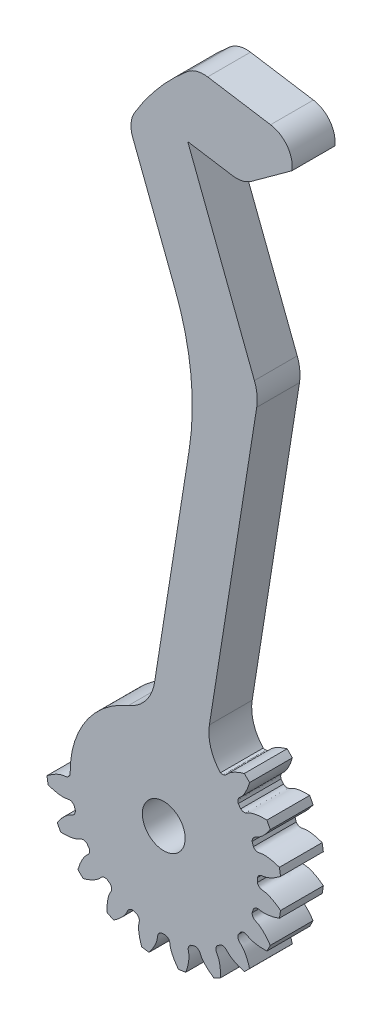
SolidWorks part; units mm, degrees
note: '?' marks a value the reader was unsure of.
material "聚脂树脂"
ref_plane "前视基准面" through (0, 0, 0) normal (0, 0, 1) x (1, 0, 0)
ref_plane "上视基准面" through (0, 0, 0) normal (0, 1, 0) x (1, 0, 0)
ref_plane "右视基准面" through (0, 0, 0) normal (1, 0, 0) x (0, 0, -1)
other "Configuration Table"
sketch "草图1" plane through (0, 0, 0) normal (0, 0, 1) x (1, 0, 0)
  circle A0 centre (0, 0) radius 13.75
extrude "凸台-拉伸1" add sketch "草图1" along normal blind 5
ref_axis "基准轴1" through (0, 0, -1.5) along (0, 0, 1)?
sketch "草图2" plane through (0, 0, 0) normal (0, 0, 1) x (1, 0, 0)
  line L0 (0, 0) -> (0, 13.75) construction
  circle A0 centre (0, 0) radius 13.75 construction
  arc A1 (0.2416, 10.9348) -> (-0.2416, 10.9348) centre (0, 0) ccw
  arc A2 (3.9764, 15.6228) -> (-3.9764, 15.6228) centre (0, 0) ccw
  spline S0 degree 3 poles (0.2416, 10.9348) (0.764, 11.1168) (0.6964, 11.4839) (0.7661, 11.8375) (0.7736, 11.8719) (0.7829, 11.9108) (0.7941, 11.954) (0.8075, 12.0015) (0.8231, 12.0532) (0.8413, 12.1091) (0.8621, 12.169) (0.8857, 12.2329) (0.9123, 12.3007) (0.9421, 12.3723) (0.9752, 12.4476) (1.0117, 12.5264) (1.0519, 12.6088) (1.0959, 12.6945) (1.1438, 12.7834) (1.1957, 12.8755) (1.2519, 12.9705) (1.3125, 13.0684) (1.3775, 13.1691) (1.4472, 13.2723) (1.5216, 13.3779) (1.601, 13.4858) (1.6853, 13.5958) (1.7747, 13.7078) (1.8694, 13.8216) (1.9693, 13.937) (2.0748, 14.0539) (2.1857, 14.1721) (2.3023, 14.2914) (2.4246, 14.4116) (2.5527, 14.5326) (2.6866, 14.6542) (2.8265, 14.7761) (2.9725, 14.8983) (3.1245, 15.0204) (3.2826, 15.1424) (3.4469, 15.2639) (3.6768, 15.427) (3.8549, 15.5454) (3.9764, 15.6228) knots 0 0 0 0 0.165916 0.170906 0.176664 0.183189 0.190482 0.198542 0.207371 0.216967 0.22733 0.238462 0.250361 0.263027 0.276462 0.290664 0.305634 0.321371 0.337876 0.355149 0.37319 0.391998 0.411574 0.431917 0.453028 0.474907 0.497554 0.520968 0.54515 0.570099 0.595817 0.622302 0.649554 0.677575 0.706363 0.735918 0.766242 0.797333 0.829191 0.861818 0.895212 0.929373 1 1 1 1
  spline S1 degree 3 poles (-0.2416, 10.9348) (-0.764, 11.1168) (-0.6964, 11.4839) (-0.7661, 11.8375) (-0.7736, 11.8719) (-0.7829, 11.9108) (-0.7941, 11.954) (-0.8075, 12.0015) (-0.8231, 12.0532) (-0.8413, 12.1091) (-0.8621, 12.169) (-0.8857, 12.2329) (-0.9123, 12.3007) (-0.9421, 12.3723) (-0.9752, 12.4476) (-1.0117, 12.5264) (-1.0519, 12.6088) (-1.0959, 12.6945) (-1.1438, 12.7834) (-1.1957, 12.8755) (-1.2519, 12.9705) (-1.3125, 13.0684) (-1.3775, 13.1691) (-1.4472, 13.2723) (-1.5216, 13.3779) (-1.601, 13.4858) (-1.6853, 13.5958) (-1.7747, 13.7078) (-1.8694, 13.8216) (-1.9693, 13.937) (-2.0748, 14.0539) (-2.1857, 14.1721) (-2.3023, 14.2914) (-2.4246, 14.4116) (-2.5527, 14.5326) (-2.6866, 14.6542) (-2.8265, 14.7761) (-2.9725, 14.8983) (-3.1245, 15.0204) (-3.2826, 15.1424) (-3.4469, 15.2639) (-3.6768, 15.427) (-3.8549, 15.5454) (-3.9764, 15.6228) knots 0 0 0 0 0.165916 0.170906 0.176664 0.183189 0.190482 0.198542 0.207371 0.216967 0.22733 0.238462 0.250361 0.263027 0.276462 0.290664 0.305634 0.321371 0.337876 0.355149 0.37319 0.391998 0.411574 0.431917 0.453028 0.474907 0.497554 0.520968 0.54515 0.570099 0.595817 0.622302 0.649554 0.677575 0.706363 0.735918 0.766242 0.797333 0.829191 0.861818 0.895212 0.929373 1 1 1 1
extrude "切除-拉伸1" cut sketch "草图2" along normal through all
pattern_circular "阵列(圆周)1" count 20 every 18 about axis through (0, 0, -1.5) along (0, 0, 1) of "切除-拉伸1"
sketch "草图6" plane through (0, 0, 0) normal (0, 0, -1) x (-1, 0, 0)
  line L0 (0, 0) -> (-10.311, 65.1009) construction
  line L1 (0, 0) -> (38.9643, 6.1713) construction
  line L2 (0, 0) -> (-30.4582, -4.8241) construction
  line L3 (-12.3461, -1.9554) -> (-25.9319, 83.8219) construction
  line L4 (3.21, 0.5084) -> (-2.4333, 36.1385)
  line L5 (-3.21, -0.5084) -> (-8.8532, 35.1216)
  line L6 (-8.8532, 35.1216) -> (-14.8239, 72.819)
  line L7 (-14.8239, 72.819) -> (-21.4537, 55.5478) construction
  line L8 (-14.8239, 72.819) -> (-7.9754, 90.6601) construction
  line L9 (-14.8239, 72.819) -> (-11.7149, 80.9182)
  line L10 (-3.21, -0.5084) -> (3.21, 0.5084)
  line L11 (-25.2081, 79.2523) -> (-40.1052, 40.4441)
  line L12 (-40.1052, 40.4441) -> (0.9522, 46.947)
  line L13 (0.9522, 46.947) -> (-25.2081, 79.2523)
  line L14 (-15.4429, 76.7274) -> (6.8442, 49.2051)
  line L15 (-17.6993, 31.8433) -> (-2.8022, 70.6515)
  line L16 (-2.8022, 70.6515) -> (-43.8596, 64.1486)
  line L17 (-43.8596, 64.1486) -> (-17.6993, 31.8433)
  line L18 (-2.4333, 36.1385) -> (-3.0647, 40.1255)
  line L19 (-3.0647, 40.1255) -> (-4.2206, 47.4234)
  line L20 (-4.2206, 47.4234) -> (4.1358, 69.1925)
  line L21 (-14.8239, 72.819) -> (-15.4429, 76.7274)
  line L22 (-15.4429, 76.7274) -> (-3.8174, 78.5687)
  circle A0 centre (0, 0) radius 12.5 construction
  circle A1 centre (-21.4537, 55.5478) radius 24 construction
  circle A2 centre (-21.4537, 55.5478) radius 27.1754 construction
  arc A3 (-11.7149, 80.9182) -> (-2.4333, 36.1385) centre (-21.4537, 55.5478) cw
  arc A4 (-12.8529, 77.9537) -> (-8.8532, 35.1216) centre (-21.4537, 55.5478) cw
  arc A5 (6.8442, 49.2051) -> (-2.0884, 33.9611) centre (-21.4537, 55.5478) cw
  arc A6 (0.3229, 47.7241) -> (-0.0355, 46.7905) centre (0.9522, 46.947) cw
  arc A7 (-11.061, 82.6216) -> (4.1358, 69.1925) centre (-21.4537, 55.5478) cw
  dimension "D1" = 25
  dimension "D4" = 48
  dimension "D5" = 30
  dimension "D8" = 29
  dimension "D9" = 1
  dimension "D10" = 29
  dimension "D2" = 6.5
  dimension "D3" = 58.22
  dimension "D6" = 60
  dimension "D7" = 6
  dimension "D11" = 7
extrude "凸台-拉伸2" add sketch "草图6" against normal blind 5
ref_plane "基准面1" through (12.5, 0, 0) normal (1, 0, 0) x (0, 0, -1)
ref_axis "基准轴2" through (0, 0, -6) along (0, 0, 1)?
ref_plane "基准面2" through (0, 0, 0) normal (-0.9877, 0.1564, 0) x (0, 0, 1)
ref_plane "基准面3" through (12.3461, -1.9554, 0) normal (-0.9877, 0.1564, 0) x (0, 0, 1)
sketch "草图16" plane through (0, 0, 5) normal (0, 0, 1) x (1, 0, 0)
  circle A0 centre (0, 0) radius 2.5
  dimension "D1" = 5
extrude "切除-拉伸5" cut sketch "草图16" against normal blind 16.5
sketch "草图20" plane through (0, 0, 0) normal (0, 0, -1) x (-1, 0, 0)
  line L0 (0, 0) -> (3.6089, 10.325)
  line L1 (3.6089, 10.325) -> (7.1451, 20.4421)
  line L2 (0, 0) -> (10.9348, -0.2416)
  line L3 (10.9348, -0.2416) -> (20.7519, -0.2416)
  circle A0 centre (0, 0) radius 17.5
  circle A1 centre (0, 0) radius 10.9375
  arc A2 (-8.7044, 6.6228) -> (-8.9885, 6.2318) centre (0, 0) ccw construction
  dimension "D1" = 35
extrude "切除-拉伸8" cut sketch "草图20" against normal blind 10 contours A1 L3 A0 L1
sketch "草图23" plane through (0, 0, 5) normal (0, 0, 1) x (1, 0, 0)
  line L0 (-1.2396, 12.9493) -> (-1.5763, 10.8233)
  line L1 (4.2206, 47.4234) -> (-1.2396, 12.9493) construction
  line L2 (5.1804, 11.9324) -> (4.8437, 9.8065)
  line L3 (11.0695, 49.1145) -> (5.1804, 11.9324) construction
  circle A0 centre (0, 0) radius 10.9375
  arc A1 (-1.7221, 13.6417) -> (-2.5777, 13.5062) centre (0, 0) ccw construction
  arc A2 (-1.7221, 13.6417) -> (-2.5777, 13.5062) centre (0, 0) ccw
  arc A3 (6.6252, 12.0486) -> (5.8534, 12.4419) centre (0, 0) ccw construction
  arc A4 (6.6252, 12.0486) -> (5.8534, 12.4419) centre (0, 0) ccw
  spline S0 degree 3 poles (996.9005, 66.1041) (-88.8946, -5.2942) (-13.4757, 28.9809) (-1.5748, 13.4516) (-1.4488, 13.2768) (-1.3343, 13.1037) (5.901, 1.4058) (-29.4464, -35.9501) (-982.1043, -181.6238) knots -9.021595 -9.021595 -9.021595 -9.021595 0.502446 0.525093 0.568083 0.608002 0.62681 7.30989 7.30989 7.30989 7.30989 only from (-1.7221, 13.6417) to (-1.2396, 12.9493) construction
  spline S1 degree 3 poles (-1001.8702, -39.9652) (14.2454, 6.0691) (-2.4742, 7.7001) (-2.931, 11.5081) (-2.9354, 11.558) (-2.9398, 11.6323) (-2.9424, 11.7223) (-2.941, 11.8445) (-2.9339, 11.9853) (-2.9194, 12.1444) (-2.8961, 12.3215) (-2.8626, 12.516) (-2.8175, 12.7274) (-2.7593, 12.9551) (-2.6999, 13.1539) (-2.6447, 13.3205) (3.8605, 31.7266) (86.1798, 22.4348) (-968.5361, -245.1905) knots -1.696649 -1.696649 -1.696649 -1.696649 0.165916 0.170906 0.183189 0.190482 0.207371 0.22733 0.250361 0.276462 0.305634 0.337876 0.37319 0.411574 0.453028 0.474907 0.497554 10.021595 10.021595 10.021595 10.021595 only from (-3.1492, 10.4743) to (-2.5777, 13.5062) construction
  spline S2 degree 3 poles (-1.7221, 13.6417) (-1.653, 13.5549) (-1.5348, 13.399) (-1.3791, 13.1737) (-1.2878, 13.0295) (-1.2435, 12.9558) (-1.2396, 12.9493) knots 0.492568 0.492568 0.492568 0.492568 0.546972 0.588426 0.62681 0.630575 0.630575 0.630575 0.630575
  spline S3 degree 3 poles (-3.1492, 10.4743) (-2.7087, 10.8088) (-2.8864, 11.137) (-2.931, 11.5081) (-2.9354, 11.558) (-2.9398, 11.6323) (-2.9424, 11.7223) (-2.941, 11.8445) (-2.9339, 11.9853) (-2.9194, 12.1444) (-2.8961, 12.3215) (-2.8626, 12.516) (-2.8175, 12.7274) (-2.7593, 12.9551) (-2.6866, 13.1982) (-2.6232, 13.3832) (-2.5848, 13.4873) (-2.5777, 13.5062) knots 0 0 0 0 0.165916 0.170906 0.183189 0.190482 0.207371 0.22733 0.250361 0.276462 0.305634 0.337876 0.37319 0.411574 0.453028 0.497554 0.507432 0.507432 0.507432 0.507432
  spline S4 degree 3 poles (845.3644, -532.484) (-75.0291, 47.9678) (6.1325, 31.3668) (6.6326, 11.8082) (6.6318, 11.5928) (6.6211, 11.3487) (6.6022, 11.1239) (6.5767, 10.9187) (6.5461, 10.7332) (6.5119, 10.5675) (6.4757, 10.4216) (6.4439, 10.3125) (6.4137, 10.2194) (6.3905, 10.1545) (6.3633, 10.0853) (6.3437, 10.0391) (4.7326, 6.5586) (-11.6727, 10.1742) (940.4849, -347.6039) knots -9.021595 -9.021595 -9.021595 -9.021595 0.502446 0.525093 0.568083 0.608002 0.644851 0.678629 0.709336 0.736973 0.761538 0.783033 0.792629 0.809518 0.816811 0.829094 0.834084 2.696649 2.696649 2.696649 2.696649 only from (6.6252, 12.0486) to (6.2318, 8.9885) construction
  spline S5 degree 3 poles (877.9319, -476.2315) (16.8964, -43.2908) (-5.1779, 3.1604) (5.3183, 12.0501) (5.4807, 12.1793) (5.6544, 12.3066) (21.7717, 23.3982) (82.9078, -32.5051) (-927.6816, 370.928) knots -6.309942 -6.309942 -6.309942 -6.309942 0.37319 0.391998 0.431917 0.474907 0.497554 10.021595 10.021595 10.021595 10.021595 only from (5.1804, 11.9324) to (5.8534, 12.4419) construction
  spline S6 degree 3 poles (6.6252, 12.0486) (6.6301, 11.9377) (6.6341, 11.7422) (6.6276, 11.4683) (6.6126, 11.2338) (6.5902, 11.0188) (6.5619, 10.8235) (6.5293, 10.6479) (6.4939, 10.4921) (6.4623, 10.3749) (6.4317, 10.2737) (6.4078, 10.2024) (6.3839, 10.1378) (6.3633, 10.0853) (6.3437, 10.0391) (6.1867, 9.7) (5.9162, 9.4428) (6.2318, 8.9885) knots 0.492568 0.492568 0.492568 0.492568 0.546972 0.588426 0.62681 0.662124 0.694366 0.723538 0.749639 0.77267 0.783033 0.801458 0.809518 0.816811 0.829094 0.834084 1 1 1 1
  spline S7 degree 3 poles (5.1804, 11.9324) (5.2452, 11.9889) (5.3764, 12.0981) (5.5842, 12.2567) (5.7442, 12.3691) (5.8366, 12.4308) (5.8534, 12.4419) knots 0.369425 0.369425 0.369425 0.369425 0.411574 0.453028 0.497554 0.507432 0.507432 0.507432 0.507432
extrude "切除-拉伸10" cut sketch "草图23" against normal blind 10 contours S3 A0 L0 S2 A2 | S7 L2 A0 S6 A4
fillet "圆角7" radius 5 2 edges at (4.8437, 9.8065, 2.5) (-1.5763, 10.8233, 2.5)
fillet "圆角8" radius 3 3 edges at (-4.1358, 69.1925, 2.5) (3.8174, 78.5687, 2.5) (15.4429, 76.7274, 2.5)
chamfer "倒角1" distance 5 angle 45 1 edges at (14.1948, 68.8471, 2.5)
fillet "圆角9" radius 5 1 edges at (11.0695, 49.1145, 2.5)
fillet "圆角10" radius 30 1 edges at (4.2206, 47.4234, 2.5)
fillet "圆角11" radius 3 1 edges at (9.2564, 69.6292, 2.5)
